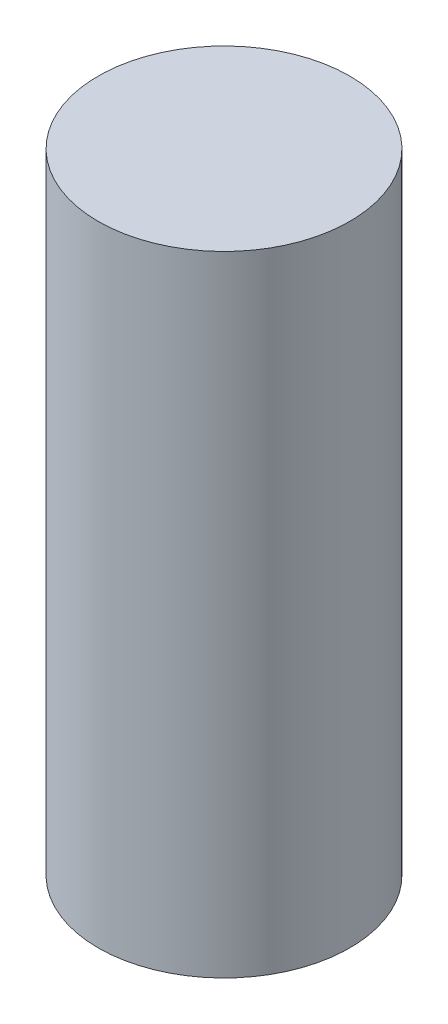
SolidWorks part; units mm, degrees
ref_plane "Plan de face" through (0, 0, 0) normal (0, 0, 1) x (1, 0, 0)
ref_plane "Plan de dessus" through (0, 0, 0) normal (0, 1, 0) x (1, 0, 0)
ref_plane "Plan de droite" through (0, 0, 0) normal (1, 0, 0) x (0, 0, -1)
sketch "Esquisse1" plane through (0, 0, 0) normal (0, 1, 0) x (1, 0, 0)
  circle A0 centre (0, 0) radius 2
  dimension "D1" = 4
extrude "Boss.-Extru.1" add sketch "Esquisse1" along normal blind 10
